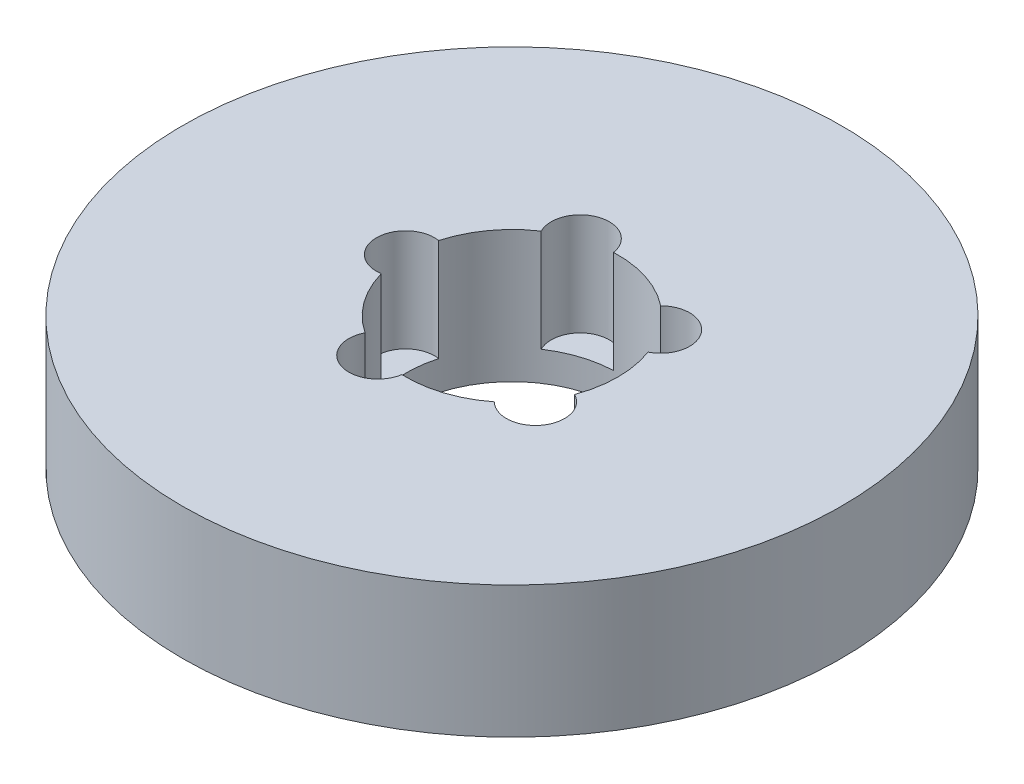
SolidWorks part; units mm, degrees
ref_plane "Front Plane" through (0, 0, 0) normal (0, 0, 1) x (1, 0, 0)
ref_plane "Top Plane" through (0, 0, 0) normal (0, 1, 0) x (1, 0, 0)
ref_plane "Right Plane" through (0, 0, 0) normal (1, 0, 0) x (0, 0, -1)
sketch "Sketch1" plane through (0, 0, 0) normal (0, 1, 0) x (1, 0, 0)
  circle A0 centre (0, 0) radius 70
  dimension "FLANGE_OD" = 140
extrude "Boss-Extrude1" add sketch "Sketch1" along normal blind 28
sketch "Sketch2" plane through (0, 0, 0) normal (0, 1, 0) x (1, 0, 0)
  circle A0 centre (0, 0) radius 22.5
  dimension "BORE_D" = 45
extrude "Cut-Extrude1" cut sketch "Sketch2" along normal through all
sketch "Sketch3" plane through (0, 28, 0) normal (0, 1, 0) x (1, 0, 0)
  circle A0 centre (0, 0) radius 22.606 construction
  circle A1 centre (-22.606, 0) radius 6.1739
  dimension "BOLT_D" = 12.3478
  dimension "BOLT_PCD" = 45.2121
extrude "Cut-Extrude2" cut sketch "Sketch3" against normal blind 21.7277
pattern_circular "CirPattern1" count 5 over 360 about axis through (0, 0, 0) along (0, 1, 0) of "Cut-Extrude2"
